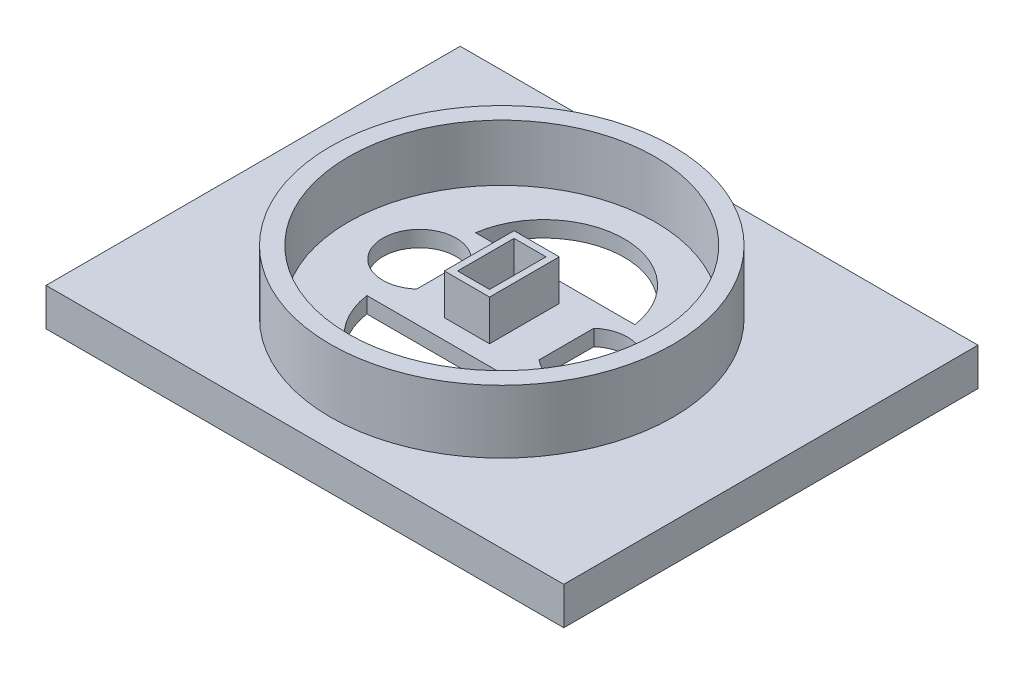
SolidWorks part; units mm, degrees
ref_plane "Front Plane" through (0, 0, 0) normal (0, 0, 1) x (1, 0, 0)
ref_plane "Top Plane" through (0, 0, 0) normal (0, 1, 0) x (1, 0, 0)
ref_plane "Right Plane" through (0, 0, 0) normal (1, 0, 0) x (0, 0, -1)
sketch "Sketch4" plane through (0, 0, 0) normal (0, 1, 0) x (1, 0, 0)
  line L0 (0, -46.7905) -> (24.3942, -46.7905) construction
  line L1 (0, -46.7905) -> (0, -24.9936) construction
  circle A0 centre (0, -46.7905) radius 17
  dimension "D1" = 34
extrude "Boss-Extrude3" add sketch "Sketch4" along normal blind 6 separate body
shell "Shell4" thickness 0.5 removed face at (0, 6, 63.7905) outward yes
ref_plane "Plane2" through (0, 0, 0) normal (0, 1, 0) x (1, 0, 0)
sketch "Sketch5" plane through (0, 0, 0) normal (0, 1, 0) x (1, 0, 0)
  line L0 (17, -46.7905) -> (-25.0436, -46.7905) construction
  line L1 (1.7, -43.7905) -> (-1.7, -43.7905)
  line L2 (1.7, -43.7905) -> (1.7, -49.7905)
  line L3 (1.7, -49.7905) -> (-1.7, -49.7905)
  line L4 (-1.7, -43.7905) -> (-1.7, -49.7905)
  line L5 (0, -29.7905) -> (0, -85.3723) construction
  circle A0 centre (0, -46.7905) radius 17 construction
  circle A1 centre (0, -46.7905) radius 17 construction
  dimension "D1" = 6
  dimension "D2" = 3.4
  dimension "D3" = 3
  dimension "D4" = 1.7
extrude "Boss-Extrude4" add sketch "Sketch5" along normal blind 5
shell "Shell5" thickness 0.7 removed face at (0, 5, 46.7905) outward yes
sketch "Sketch6" plane through (0, 0, 0) normal (0, 1, 0) x (1, 0, 0)
  line L1 (27.7675, -23.9741) -> (-27.2325, -23.9741)
  line L2 (27.7675, -23.9741) -> (27.7675, -67.9741)
  line L3 (27.7675, -67.9741) -> (-27.2325, -67.9741)
  line L4 (-27.2325, -23.9741) -> (-27.2325, -67.9741)
  dimension "D1" = 55
  dimension "D2" = 44
extrude "Boss-Extrude5" add sketch "Sketch6" against normal blind 4 contours L2 L1 L4 L3
sketch "Sketch7" plane through (0, -4, 0) normal (0, -1, 0) x (-1, 0, 0)
  line L1 (-26.3354, -25.4801) -> (25.919, -25.4801)
  line L2 (-26.3354, -25.4801) -> (-26.3354, -66.5709)
  line L3 (-26.3354, -66.5709) -> (25.919, -66.5709)
  line L4 (25.919, -25.4801) -> (25.919, -66.5709)
extrude "Cut-Extrude1" cut sketch "Sketch7" against normal blind 3
sketch "Sketch8" plane through (0, 0.7, 0) normal (0, 1, 0) x (1, 0, 0)
  line L0 (-8.5548, -41.0152) -> (8.3542, -41.0152)
  line L1 (2.4, -46.7905) -> (31.3222, -46.7905) construction
  line L2 (2.4, -50.4905) -> (2.4, -43.0905) construction
  line L3 (-8.5548, -52.5657) -> (8.3542, -52.5657)
  line L4 (-6.5068, -43.5287) -> (-6.5068, -49.3295)
  line L5 (0, -43.0905) -> (0, -27.4386) construction
  line L6 (2.4, -43.0905) -> (-2.4, -43.0905) construction
  line L7 (6.5068, -43.5287) -> (6.5068, -49.3295)
  arc A0 (-8.5548, -41.0152) -> (8.3542, -41.0152) centre (-0.1003, -42.217) cw
  arc A1 (-8.5548, -52.5657) -> (8.3542, -52.5657) centre (-0.1003, -51.3639) ccw
  arc A2 (-6.5068, -43.5287) -> (-6.5068, -49.3295) centre (-9.1002, -46.4291) ccw
  arc A3 (6.5068, -43.5287) -> (6.5068, -49.3295) centre (9.1002, -46.4291) cw
extrude "Cut-Extrude2" cut sketch "Sketch8" against normal through all
